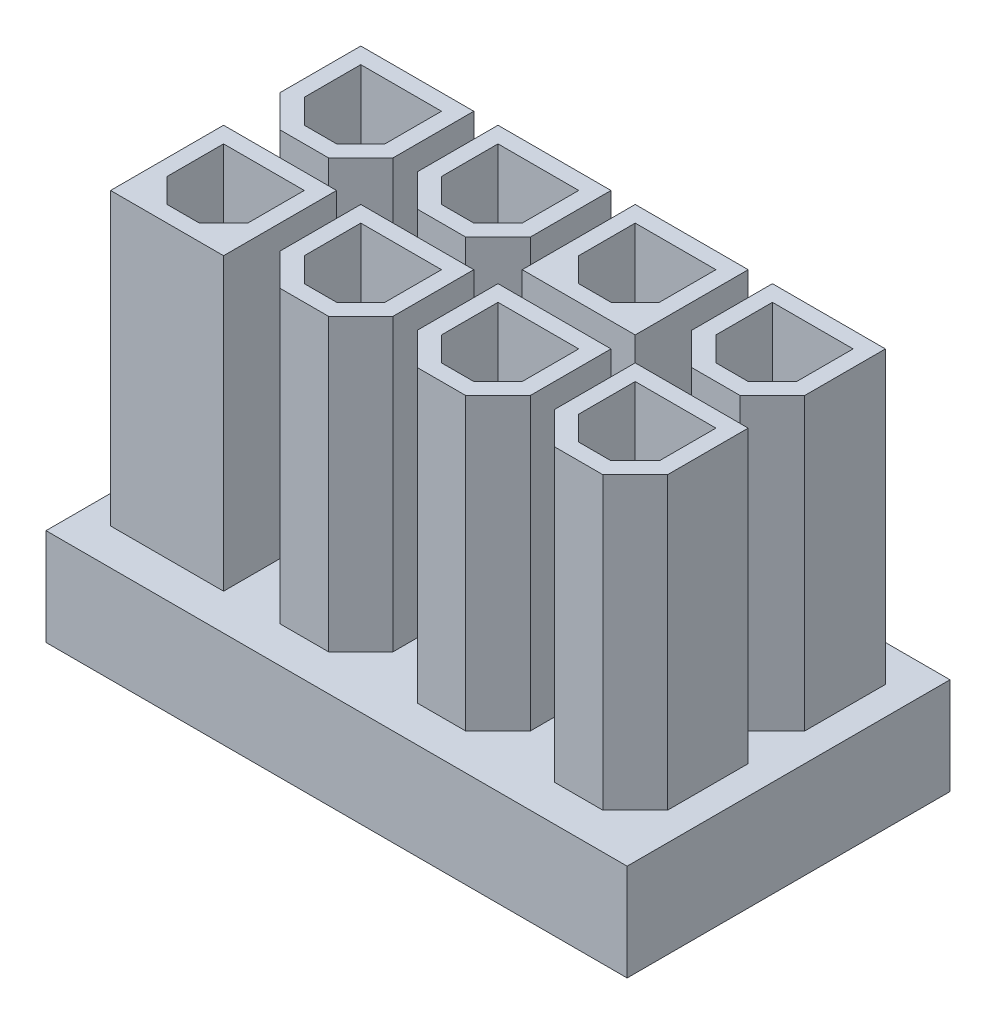
SolidWorks part; units mm, degrees
ref_plane "Ebene vorne" through (0, 0, 0) normal (0, 0, 1) x (1, 0, 0)
ref_plane "Ebene oben" through (0, 0, 0) normal (0, 1, 0) x (1, 0, 0)
ref_plane "Ebene rechts" through (0, 0, 0) normal (1, 0, 0) x (0, 0, -1)
sketch "Skizze1" plane through (0, 0, 0) normal (1, 0, 0) x (0, 0, -1)
  line L1 (5, 0) -> (-5, 0)
  line L2 (5, 0) -> (5, 11)
  line L3 (5, 11) -> (-5, 11)
  line L4 (-5, 0) -> (-5, 11)
  point P4 (0, 0)
  dimension "D1" = 10
  dimension "D2" = 11
extrude "Aufsatz-Linear austragen1" add sketch "Skizze1" along normal mid plane 18
sketch "Skizze2" plane through (0, 0, 0) normal (1, 0, 0) x (0, 0, -1)
  line L0 (0, 0) -> (0, 11) construction
  line L1 (-5, 0) -> (-6.5, 0)
  line L2 (-5, 0) -> (-5, 1)
  line L3 (-5, 1) -> (-6.5, 1)
  line L4 (-6.5, 0) -> (-6.5, 1)
  line L5 (5, 11) -> (-5, 11) construction
  line L6 (6.5, 0) -> (6.5, 1)
  line L7 (5, 1) -> (6.5, 1)
  line L8 (5, 0) -> (5, 1)
  line L9 (5, 0) -> (6.5, 0)
  dimension "D1" = 1.5
  dimension "D2" = 1
extrude "Aufsatz-Linear austragen2" add sketch "Skizze2" along normal mid plane 18
sketch "Skizze3" plane through (0, 0, 0) normal (1, 0, 0) x (0, 0, -1)
  line L0 (5, 11) -> (5.5717, 11)
  line L1 (7.5, 8.198) -> (7.5, 5.198)
  line L2 (7.5, 5.198) -> (8.5, 4)
  line L3 (8.5, 4) -> (8.5, 2)
  line L4 (8.5, 2) -> (6.5, 2)
  line L5 (6.5, 2) -> (6.5, 8)
  line L6 (6.5, 8) -> (5, 8)
  line L7 (5, 1) -> (5, 11) construction
  line L8 (5, 11) -> (5, 8)
  line L9 (-6.5, 0) -> (6.5, 0) construction
  arc A0 (5.5717, 11) -> (6.5359, 9.599) centre (7.0717, 11) ccw
  arc A1 (6.5359, 9.599) -> (7.5, 8.198) centre (6, 8.198) cw
  dimension "D5" = 1.5
  dimension "D1" = 2
  dimension "D2" = 1
  dimension "D3" = 2
  dimension "D4" = 2
  dimension "D6" = 3
  dimension "D7" = 1.5
  dimension "D8" = 3
extrude "Aufsatz-Linear austragen3" [suppressed] add sketch "Skizze3" along normal mid plane 8
sketch "Skizze4" [suppressed] plane through (0, 0, 0) normal (0, -1, 0) x (1, 0, 0)
  line L0 (9, -5) -> (-9, -5) construction
  line L1 (-2.5, -5) -> (2.5, -5)
  line L2 (-2.5, -5) -> (-2.5, -6.5)
  line L3 (-2.5, -6.5) -> (2.5, -6.5)
  line L4 (2.5, -5) -> (2.5, -6.5)
  line L5 (9, -6.5) -> (-9, -6.5) construction
  line L6 (0, -5) -> (0, 0) construction
  line L7 (-4, -6.5) -> (-4, -8.5) construction
  dimension "D1" = 1.5
extrude "Schnitt-Linear austragen1" [suppressed] cut sketch "Skizze4" against normal through all
sketch "Skizze5" [suppressed] plane through (0, 0, 0) normal (1, 0, 0) x (0, 0, -1)
  line L0 (8.1235, 4.451) -> (8.1235, 19.8707)
  line L1 (8.5, 4) -> (7.5, 5.198) construction
  line L2 (8.1235, 19.8707) -> (7.1363, 21)
  line L3 (7.1363, 21) -> (6.1363, 21)
  line L4 (6.1363, 21) -> (4.6235, 19.6776)
  line L5 (4.6235, 19.6776) -> (4.6235, 17.6776)
  line L6 (4.6235, 17.6776) -> (6.1235, 17.6776)
  line L7 (6.1235, 17.6776) -> (6.5, 8)
  line L8 (6.5, 8) -> (6.5, 2)
  line L9 (6.5, 2) -> (8.1235, 4.451)
  line L10 (5, 11) -> (-5, 11) construction
  dimension "D1" = 3.5
  dimension "D2" = 1.5
  dimension "D3" = 1
  dimension "D4" = 10
  dimension "D5" = 2
  dimension "D6" = 2.0093
  dimension "D7" = 1.5
extrude "Aufsatz-Linear austragen4" [suppressed] add sketch "Skizze5" along normal mid plane 5
sketch "Skizze6" plane through (0, 0, 0) normal (0, -1, 0) x (1, 0, 0)
  line L0 (-9, 6.5) -> (-9, -6.5) construction
  line L1 (-8.25, -4) -> (-4.5, -4)
  line L2 (-8.25, -4) -> (-8.25, -0.25)
  line L3 (-8.25, -0.25) -> (-4.5, -0.25)
  line L4 (-4.5, -4) -> (-4.5, -0.25)
  line L5 (9, -5) -> (-9, -5) construction
  dimension "D1" = 0.75
  dimension "D2" = 1
  dimension "D3" = 3.75
extrude "Schnitt-Linear austragen2" cut sketch "Skizze6" against normal blind 10
pattern_linear "Lineares Muster1" count 4 spacing 4.25 along (1, 0, 0) count 2 spacing 4.25 along (0, 0, 1) of "Schnitt-Linear austragen2"
sketch "Skizze7" plane through (0, 11, 0) normal (0, 1, 0) x (1, 0, 0)
  line L1 (-4.5, -0.25) -> (-8.25, -4) construction
  line L2 (-8.25, -0.25) -> (-4.5, -4) construction
  line L4 (-8.125, -0.375) -> (-4.625, -0.375)
  line L6 (-8.125, -0.375) -> (-8.125, -3.875)
  line L8 (-8.125, -3.875) -> (-4.625, -3.875)
  line L10 (-4.625, -0.375) -> (-4.625, -3.875)
  line L11 (-8.125, -0.375) -> (-4.625, -3.875) construction
  point P4 (-6.375, -2.125)
  dimension "D1" = 3.5
extrude "Aufsatz-Linear austragen5" add sketch "Skizze7" along normal blind 9
pattern_linear "Lineares Muster2" count 3 spacing 4.25 along (1, 0, 0) count 2 spacing 4.25 along (0, 0, -1) skipping (0, 1), (1, 0), (1, 1), (2, 0) of "Aufsatz-Linear austragen5"
sketch "Skizze10" plane through (0, 11, 0) normal (0, 1, 0) x (1, 0, 0)
  line L0 (-8.25, 4) -> (-4.5, 0.25) construction
  line L1 (-4.5, 4) -> (-8.25, 0.25) construction
  line L3 (-4.625, 1.375) -> (-5.625, 0.375)
  line L5 (-5.625, 0.375) -> (-7.125, 0.375)
  line L6 (-4.625, 1.375) -> (-4.625, 3.875)
  line L7 (-4.625, 3.875) -> (-8.125, 3.875)
  line L8 (-8.125, 1.375) -> (-8.125, 3.875)
  line L9 (-4.625, 0.375) -> (-8.125, 3.875) construction
  line L10 (-4.625, 3.875) -> (-8.125, 0.375) construction
  line L11 (-7.125, 0.375) -> (-8.125, 1.375)
  point P4 (-6.375, 2.125)
  dimension "D1" = 3.5
extrude "Aufsatz-Linear austragen7" add sketch "Skizze10" along normal up to surface (9 mm away) up to face at (-6.375, 20, 2.125)
pattern_linear "Lineares Muster4" count 4 spacing 4.25 along (1, 0, 0) count 2 spacing 4.25 along (0, 0, 1) skipping (0, 1), (2, 0) of "Aufsatz-Linear austragen7"
sketch "Skizze12" plane through (0, 20, 0) normal (0, 1, 0) x (1, 0, 0)
  line L16 (-8.25, 2.125) -> (-4.5, 2.125) construction
  line L17 (-6.375, 4) -> (-6.375, 0.25) construction
  line L18 (-8.25, 4) -> (-3.0668, -1.1832) construction
  line L19 (-5.875, 0.875) -> (-5.125, 1.625)
  line L20 (-7.625, 3.375) -> (-5.125, 3.375)
  line L21 (-7.625, 3.375) -> (-7.625, 1.625)
  line L22 (-6.875, 0.875) -> (-5.875, 0.875)
  line L23 (-5.125, 3.375) -> (-5.125, 1.625)
  line L24 (-7.625, 3.375) -> (-5.125, 0.875) construction
  line L25 (-7.625, 0.875) -> (-5.125, 3.375) construction
  line L26 (-7.625, 1.625) -> (-6.875, 0.875)
  line L27 (-4.5, 4) -> (-4.5, 0.25) construction
  line L28 (-8.25, 0.25) -> (-8.25, 4) construction
  line L29 (-8.25, 4) -> (-4.5, 4) construction
  line L30 (-4.5, 0.25) -> (-8.25, 0.25) construction
  point P35 (-6.375, 2.125)
  dimension "D1" = 2.5
  dimension "D3" = 0.75
  dimension "D4" = 0.75
  dimension "D5" = 0.75
  dimension "D6" = 0.75
  dimension "D7" = 2.5
extrude "Schnitt-Linear austragen4" cut sketch "Skizze12" against normal through all
pattern_linear "Lineares Muster6" count 4 spacing 4.25 along (1, 0, 0) count 2 spacing 4.25 along (0, 0, 1) of "Schnitt-Linear austragen4"
sketch "草图2" plane through (0, 10, 0) normal (0, -1, 0) x (-1, 0, 0)
  point P8 (-6.375, -2.125)
  point P9 (-6.375, 2.125)
  point P10 (-2.125, 2.125)
  point P11 (-2.125, -2.125)
  point P12 (2.125, -2.125)
  point P13 (2.125, 2.125)
  point P14 (6.375, -2.125)
  point P15 (6.375, 2.125)
other "连接点1" parameters "直径"=2, "端头长度"=10
ref_axis "基准轴9" through (6.375, 0, -2.125) along (0, 1, 0)
other "连接点2" parameters "直径"=2, "端头长度"=10
ref_axis "基准轴10" through (6.375, 0, 2.125) along (0, 1, 0)
other "连接点3" parameters "直径"=2, "端头长度"=10
ref_axis "基准轴11" through (2.125, 0, 2.125) along (0, 1, 0)
other "连接点4" parameters "直径"=2, "端头长度"=10
ref_axis "基准轴12" through (2.125, 0, -2.125) along (0, 1, 0)
other "连接点5" parameters "直径"=2, "端头长度"=10
ref_axis "基准轴13" through (-2.125, 0, -2.125) along (0, 1, 0)
other "连接点6" parameters "直径"=2, "端头长度"=10
ref_axis "基准轴14" through (-2.125, 0, 2.125) along (0, 1, 0)
other "连接点7" parameters "直径"=2, "端头长度"=10
ref_axis "基准轴15" through (-6.375, 0, -2.125) along (0, 1, 0)
other "连接点8" parameters "直径"=2, "端头长度"=10
ref_axis "基准轴16" through (-6.375, 0, 2.125) along (0, 1, 0)
ref_axis "B2" through (6.375, 10, -2.125) along (0, -1, 0)
ref_axis "B3" through (2.125, 10, -2.125) along (0, -1, 0)
ref_axis "B4" through (-2.125, 10, -2.125) along (0, -1, 0)
ref_axis "B5" through (-6.375, 10, -2.125) along (0, -1, 0)
ref_axis "B1" through (6.375, 10, 2.125) along (0, -1, 0)
ref_axis "A1" through (2.125, 10, 2.125) along (0, -1, 0)
ref_axis "A2" through (-2.125, 10, 2.125) along (0, -1, 0)
ref_axis "A3" through (-6.375, 10, 2.125) along (0, -1, 0)
sketch "草图3" plane through (0, 0, 0) normal (0, -1, 0) x (-1, 0, 0)
  line L1 (9.6075, -10.9398) -> (-10.4636, -10.9398)
  line L2 (9.6075, -10.9398) -> (9.6075, 10.0906)
  line L3 (9.6075, 10.0906) -> (-10.4636, 10.0906)
  line L4 (-10.4636, -10.9398) -> (-10.4636, 10.0906)
extrude "切除-拉伸1" cut sketch "草图3" against normal blind 8
